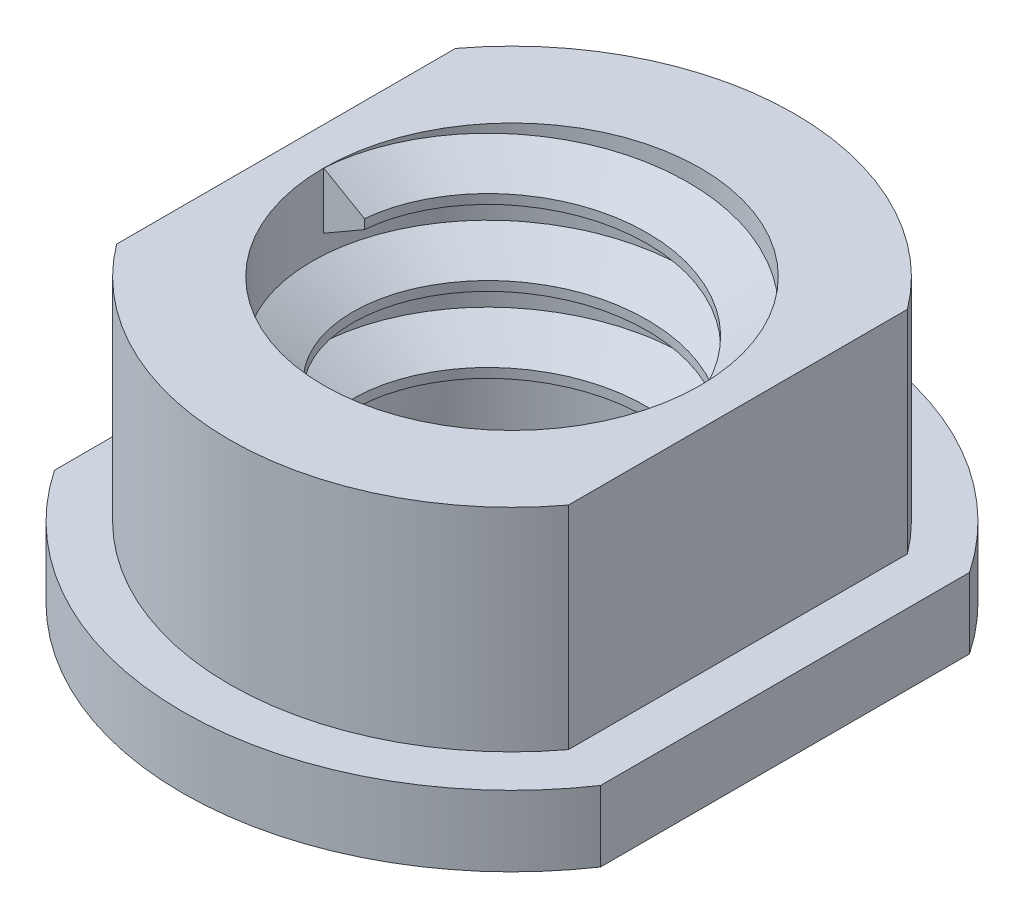
SolidWorks part; units mm, degrees
ref_plane "Front Plane" through (0, 0, 0) normal (0, 0, 1) x (1, 0, 0)
ref_plane "Top Plane" through (0, 0, 0) normal (0, 1, 0) x (1, 0, 0)
ref_plane "Right Plane" through (0, 0, 0) normal (1, 0, 0) x (0, 0, -1)
sketch "Sketch1" plane through (0, 0, 0) normal (0, 1, 0) x (1, 0, 0)
  line L0 (0, 0) -> (-14.5, 0) construction
  line L1 (0, 0) -> (14.5, 0) construction
  line L2 (-14.5, 9.798) -> (-14.5, -9.798)
  line L3 (14.5, 9.798) -> (14.5, -9.798)
  arc A1 (-14.5, 9.798) -> (14.5, 9.798) centre (0, 0) cw
  arc A2 (14.5, -9.798) -> (-14.5, -9.798) centre (0, 0) cw
extrude "Boss-Extrude1" add sketch "Sketch1" along normal mid plane 3.75
sketch "Sketch2" plane through (0, 1.875, 0) normal (0, 1, 0) x (1, 0, 0)
  line L3 (12, 9) -> (12, -9)
  line L4 (-12, 9) -> (-12, -9)
  arc A1 (-12, 9) -> (12, 9) centre (0, 0) cw
  arc A2 (-12, -9) -> (12, -9) centre (0, 0) ccw
extrude "Boss-Extrude2" add sketch "Sketch2" along normal blind 11.25
sketch "Sketch4" plane through (0, 13.125, 0) normal (0, 1, 0) x (1, 0, 0)
  circle A0 centre (0, 0) radius 10
extrude "Cut-Extrude1" cut sketch "Sketch4" against normal through all contours A0
thread "Thread1" pitch 4 start angle 0, offset 0, length 0, pitch 4, diameter 20
ref_plane "Plane1" through (-10, 13.125, 0) normal (0, 0, -1) x (1, 0, 0)
sketch "Thread Profile1" plane through (-10, 13.125, 0) normal (0, 0, -1) x (1, 0, 0)
  line L0 (0, 0) -> (0, 4) construction
  line L1 (0, 0) -> (2.1651, 1.25)
  line L2 (2.1651, 1.25) -> (2.1651, 1.75)
  line L3 (2.1651, 1.75) -> (0, 3)
  line L4 (2.1651, 1.5) -> (0, 1.5) construction
  line L11 (0, 0) -> (0, 3)
  point P2 (0, 0)
  dimension "Pitch" = 4
  dimension "Profile_Angle" = 60
  dimension "Profile_Land" = 0.5
  dimension "Profile_Height" = 2.1651
